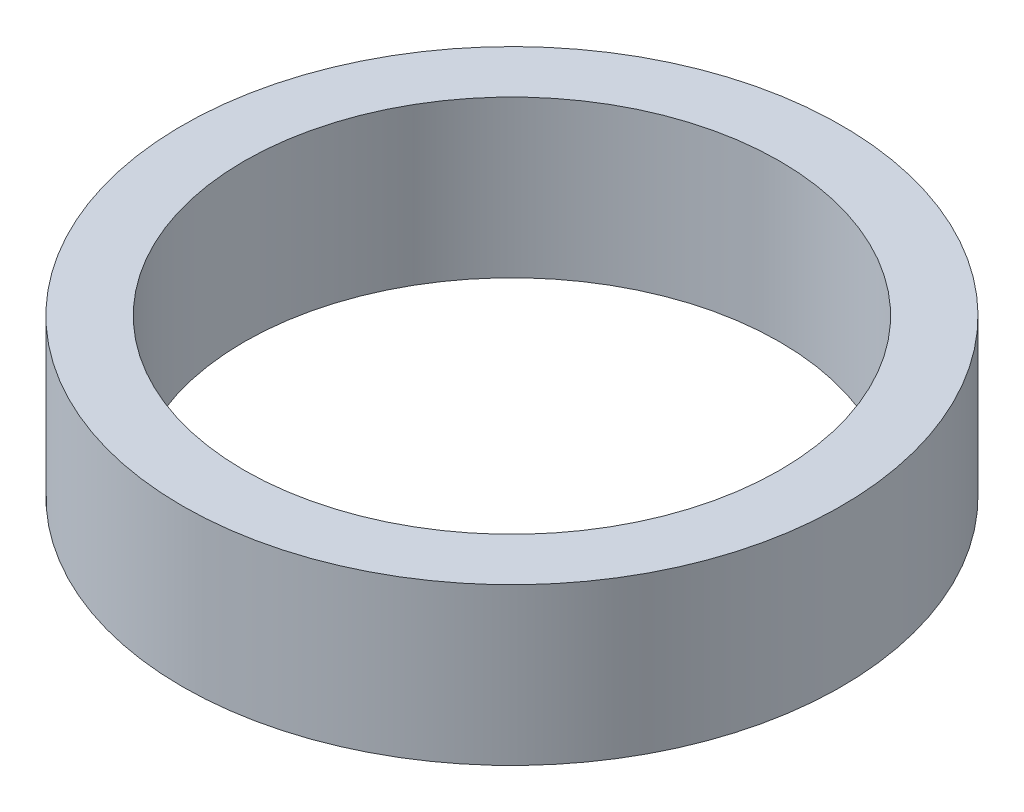
SolidWorks part; units mm, degrees
ref_plane "Front Plane" through (0, 0, 0) normal (0, 0, 1) x (1, 0, 0)
ref_plane "Top Plane" through (0, 0, 0) normal (0, 1, 0) x (1, 0, 0)
ref_plane "Right Plane" through (0, 0, 0) normal (1, 0, 0) x (0, 0, -1)
sketch "Sketch1" plane through (0, 0, 0) normal (0, 1, 0) x (1, 0, 0)
  circle A0 centre (0, 0) radius 40
  dimension "FLANGE_OD" = 80
extrude "Boss-Extrude1" add sketch "Sketch1" along normal blind 19
sketch "Sketch2" plane through (0, 0, 0) normal (0, 1, 0) x (1, 0, 0)
  circle A0 centre (0, 0) radius 32.5
  dimension "BORE_D" = 65
extrude "Cut-Extrude1" cut sketch "Sketch2" along normal through all
sketch "Sketch3" plane through (0, 19, 0) normal (0, 1, 0) x (1, 0, 0)
  circle A0 centre (0, 0) radius 17.5837 construction
  circle A1 centre (-17.5837, 0) radius 1.5
  dimension "BOLT_D" = 3
  dimension "BOLT_PCD" = 35.1675
extrude "Cut-Extrude2" cut sketch "Sketch3" against normal blind 18.7176 rebuild error yes
pattern_circular "CirPattern1" count 3 over 360 rebuild error yes
